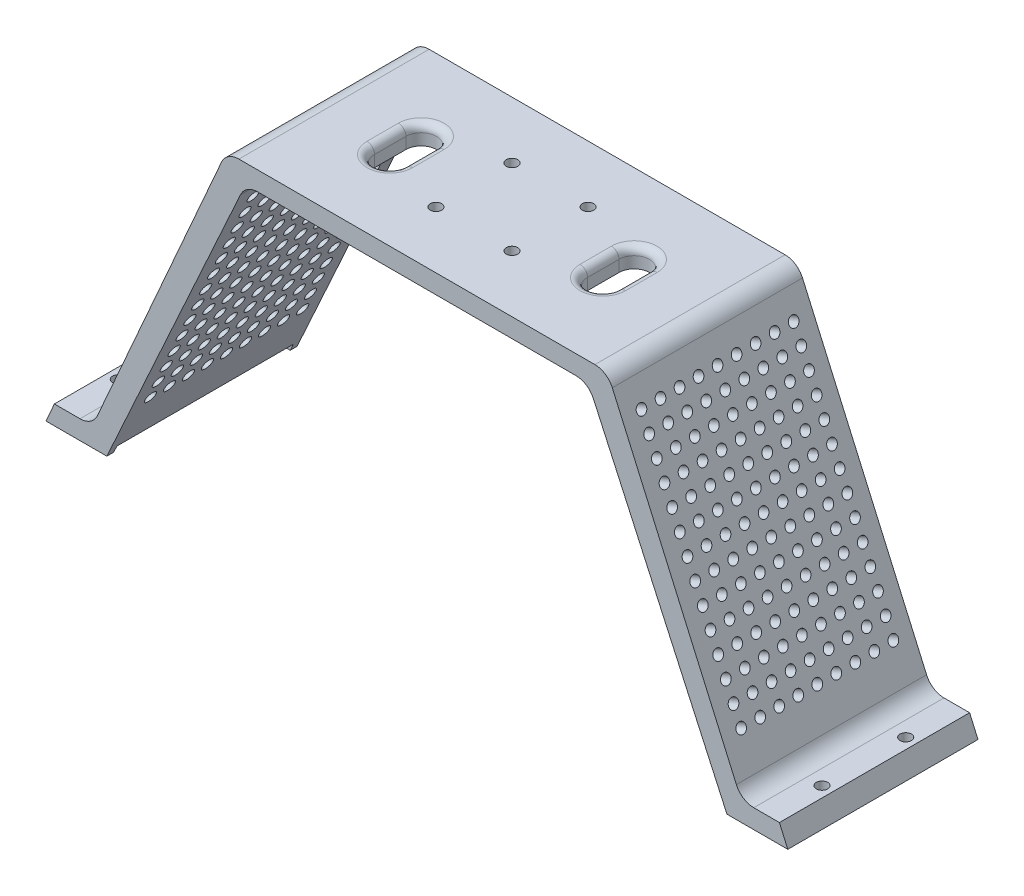
SolidWorks part; units mm, degrees
ref_plane "Front Plane" through (0, 0, 0) normal (0, 0, 1) x (1, 0, 0)
ref_plane "Top Plane" through (0, 0, 0) normal (0, 1, 0) x (1, 0, 0)
ref_plane "Right Plane" through (0, 0, 0) normal (1, 0, 0) x (0, 0, -1)
sketch "Sketch1" plane through (0, 0, 0) normal (0, 0, 1) x (1, 0, 0)
  line L0 (-87.5, 0) -> (87.5, 0)
  line L1 (-87.5, 0) -> (-50.05, 85)
  line L2 (-50.05, 85) -> (50.05, 85)
  line L3 (50.05, 85) -> (87.5, 0)
  point P4 (0, 0)
  dimension "D1" = 175
  dimension "D2" = 100.1
  dimension "D3" = 50.05
  dimension "D4" = 85
extrude "Boss-Extrude2" add sketch "Sketch1" along normal blind 50 contours L1 L2 L3 L0
sketch "Sketch3" plane through (0, 0, 50) normal (0, 0, 1) x (1, 0, 0)
  line L0 (-81.5, 0) -> (81.5, 0)
  line L1 (-87.5, 0) -> (87.5, 0) construction
  line L2 (81.5, 0) -> (45.05, 80)
  line L3 (45.05, 80) -> (-45.05, 80)
  line L4 (-45.05, 80) -> (-81.5, 0)
  line L5 (-50.05, 85) -> (50.05, 85) construction
  dimension "D1" = 163
  dimension "D2" = 6
  dimension "D3" = 90.1
  dimension "D4" = 45.05
  dimension "D5" = 5
extrude "Cut-Extrude1" cut sketch "Sketch3" against normal blind 50
fillet "Fillet1" radius 5 2 edges at (45.05, 80, 25) (-45.05, 80, 25)
sketch "Sketch5" plane through (73.2758, 32.2845, 0) normal (0.9151, 0.4032, 0) x (0, 0, -1)
  line L0 (0, 57.6053) -> (0, -35.2791) construction
  line L1 (-50, -35.2791) -> (0, -35.2791)
  line L2 (-50, -35.2791) -> (-50, -29.8151)
  line L3 (-50, -29.8151) -> (0, -29.8151)
  line L4 (0, -35.2791) -> (0, -29.8151)
  dimension "D1" = 5.464
sketch "Sketch8" plane through (0, 0, 0) normal (0, 1, 0) x (1, 0, 0)
  line L0 (93.2771, -25.8796) -> (149.3121, -25.8796)
sketch "Sketch9" plane through (0, 0, 0) normal (0, 1, 0) x (1, 0, 0)
  line L0 (-93.9767, -25.7952) -> (-133.9417, -25.7952)
sketch "Sketch10" plane through (-73.2758, 32.2845, 0) normal (-0.9151, 0.4032, 0) x (0, 0, 1)
  line L0 (0, -35.2791) -> (0, 57.6053) construction
  line L1 (50, -35.2791) -> (0, -35.2791)
  line L2 (50, -35.2791) -> (50, -29.8191)
  line L3 (50, -29.8191) -> (0, -29.8191)
  line L4 (0, -35.2791) -> (0, -29.8191)
  dimension "D1" = 5.46
extrude "Boss-Extrude4" add sketch "Sketch10" along direction (-1, 0, 0) on the side of the normal blind 10
extrude "Boss-Extrude5" add sketch "Sketch5" along direction (1, 0, 0) on the side of the normal blind 10 contours L3 L4 L1 L2
sketch "Sketch11" plane through (0, 4.9965, 0) normal (0, 1, 0) x (1, 0, 0)
  line L0 (-97.5, 0) -> (-97.5, -50) construction
  line L1 (-95.2986, -50) -> (-85.2986, -50) construction
  circle A0 centre (-92.5, -14) radius 1.5
  circle A1 centre (-92.5, -36) radius 1.5
  dimension "D1" = 22
  dimension "D2" = 5
  dimension "D3" = 14
extrude "Cut-Extrude2" cut sketch "Sketch11" against normal blind 10
sketch "Sketch12" plane through (0, 5.0002, 0) normal (0, 1, 0) x (1, 0, 0)
  line L0 (97.5, -50) -> (97.5, 0) construction
  line L1 (95.297, -50) -> (85.297, -50) construction
  circle A0 centre (92.5, -14) radius 1.5
  circle A1 centre (92.5, -36) radius 1.5
  dimension "D1" = 22
  dimension "D2" = 5
  dimension "D3" = 14
extrude "Cut-Extrude3" cut sketch "Sketch12" against normal blind 10
fillet "Fillet2" radius 5 2 edges at (85.297, 5.0002, 25) (-85.2986, 4.9965, 25)
fillet "Fillet3" radius 5 2 edges at (50.05, 85, 25) (-50.05, 85, 25)
sketch "Sketch13" plane through (0, 85, 0) normal (0, 1, 0) x (1, 0, 0)
  line L1 (-46.7892, 0) -> (-46.7892, -50) construction
  line L3 (-46.7892, 0) -> (46.7892, 0) construction
  line L4 (-46.7892, -50) -> (46.7892, -50) construction
  circle A0 centre (-9.9992, -15) radius 1.5
  circle A1 centre (10.0008, -15) radius 1.5
  circle A2 centre (-9.9992, -35) radius 1.5
  circle A3 centre (10.0008, -35) radius 1.5
  dimension "D1" = 20
  dimension "D2" = 20
  dimension "D3" = 20
  dimension "D4" = 20
  dimension "D5" = 36.79
  dimension "D6" = 15
extrude "Cut-Extrude5" cut sketch "Sketch13" against normal blind 10
sketch "Sketch14" plane through (0, 80, 0) normal (0, -1, 0) x (1, 0, 0)
  circle A0 centre (-9.9992, 35) radius 3
  circle A1 centre (-9.9992, 15) radius 3
  circle A2 centre (10.0008, 35) radius 3
  circle A3 centre (10.0008, 15) radius 3
extrude "Cut-Extrude6" cut sketch "Sketch14" against normal blind 2.5
sketch "Sketch15" plane through (0, 85, 0) normal (0, 1, 0) x (1, 0, 0)
  line L0 (-27.9992, -20.87) -> (-27.9992, -29.13) construction
  line L1 (-23.9992, -20.87) -> (-23.9992, -29.13)
  line L2 (-31.9992, -20.87) -> (-31.9992, -29.13)
  line L3 (28.0008, -20.87) -> (28.0008, -29.13) construction
  line L4 (32.0008, -20.87) -> (32.0008, -29.13)
  line L5 (24.0008, -20.87) -> (24.0008, -29.13)
  line L6 (-46.7892, 0) -> (46.7892, 0) construction
  line L7 (-46.7892, -50) -> (46.7892, -50) construction
  arc A0 (-23.9992, -20.87) -> (-31.9992, -20.87) centre (-27.9992, -20.87) ccw
  arc A1 (-31.9992, -29.13) -> (-23.9992, -29.13) centre (-27.9992, -29.13) ccw
  arc A2 (32.0008, -20.87) -> (24.0008, -20.87) centre (28.0008, -20.87) ccw
  arc A3 (24.0008, -29.13) -> (32.0008, -29.13) centre (28.0008, -29.13) ccw
  circle A4 centre (-9.9992, -15) radius 1.5 construction
  circle A5 centre (10.0008, -15) radius 1.5 construction
  point P2 (-27.9992, -25)
  point P7 (28.0008, -25)
  point P14 (28.0008, -16.87)
  dimension "D5" = 20.87
  dimension "D1" = 4
  dimension "D2" = 4
  dimension "D3" = 18
  dimension "D4" = 18
  dimension "D6" = 20.87
  dimension "D7" = 20.87
  dimension "D8" = 20.87
extrude "Cut-Extrude8" cut sketch "Sketch15" against normal blind 8.5
fillet "Fillet5" radius 2 8 edges at (-27.9992, 85, 33.13) (-23.9992, 85, 25) (-31.9992, 85, 25) (-27.9992, 85, 16.87) (28.0008, 85, 16.87) (32.0008, 85, 25) (24.0008, 85, 25) (28.0008, 85, 33.13)
sketch "Sketch16" plane through (73.2758, 32.2845, 0) normal (0.9151, 0.4032, 0) x (0, 0, -1)
  line L0 (-50, 54.3444) -> (-50, -26.5542) construction
  circle A0 centre (-45, 47.7106) radius 1.3
  dimension "D1" = 5
extrude "Cut-Extrude9" cut sketch "Sketch16" against normal blind 12
pattern_linear "LPattern1" count 9 spacing 5 along (0, 0, -1) count 14 spacing 5 along (0.4032, -0.9151, 0) of "Cut-Extrude9"
sketch "Sketch17" plane through (-73.2758, 32.2845, 0) normal (-0.9151, 0.4032, 0) x (0, 0, 1)
  line L0 (0, -26.5582) -> (0, 54.3444) construction
  line L1 (50, 54.3444) -> (0, 54.3444) construction
  circle A0 centre (5, 47.7144) radius 1.5
  dimension "D1" = 5
  dimension "D2" = 6.63
extrude "Cut-Extrude10" cut sketch "Sketch17" against normal blind 12
pattern_linear "LPattern2" count 9 spacing 5 along (0, 0, 1) count 14 spacing 5 along (-0.4032, -0.9151, 0) of "Cut-Extrude10"
sketch "Sketch18" plane through (0, 0, 0) normal (0, -1, 0) x (1, 0, 0)
  line L0 (81.5, 0) -> (97.5, 0) construction
  line L1 (95.7, 1.8) -> (80.5, 1.8)
  line L2 (95.7, 1.8) -> (95.7, 48.2)
  line L3 (95.7, 48.2) -> (80.5, 48.2)
  line L4 (80.5, 1.8) -> (80.5, 48.2)
  line L5 (97.5, 50) -> (97.5, 0) construction
  line L6 (81.5, 50) -> (97.5, 50) construction
  dimension "D1" = 1.8
  dimension "D2" = 1.8
  dimension "D3" = 1.8
  dimension "D4" = 15.2
extrude "Cut-Extrude14" cut sketch "Sketch18" against normal blind 1.8 contours L1 L4 L3 L2
sketch "Sketch19" plane through (0, 0, 0) normal (0, -1, 0) x (1, 0, 0)
  line L0 (-97.5, 0) -> (-81.5, 0) construction
  line L1 (-95.7, 1.8) -> (-80.5, 1.8)
  line L2 (-95.7, 1.8) -> (-95.7, 48.2)
  line L3 (-95.7, 48.2) -> (-80.5, 48.2)
  line L4 (-80.5, 1.8) -> (-80.5, 48.2)
  line L5 (-97.5, 0) -> (-97.5, 50) construction
  line L6 (-97.5, 50) -> (-81.5, 50) construction
  dimension "D1" = 1.8
  dimension "D2" = 1.8
  dimension "D3" = 1.8
  dimension "D4" = 15.2
extrude "Cut-Extrude15" cut sketch "Sketch19" against normal blind 1.8
